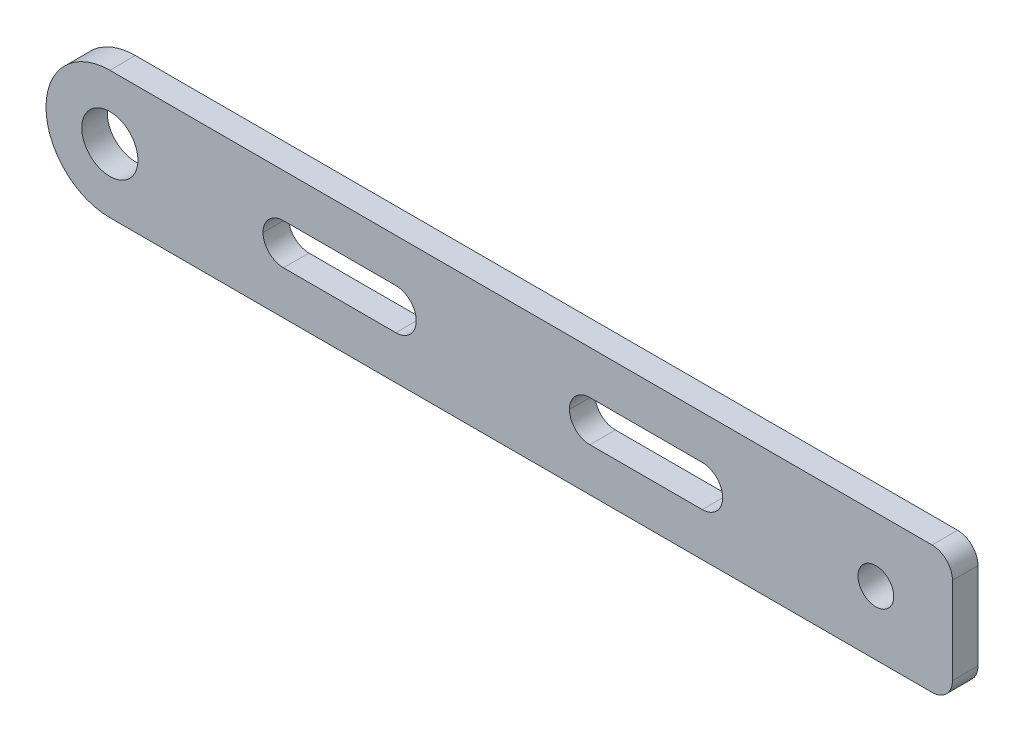
SolidWorks part; units mm, degrees
ref_plane "Front Plane" through (0, 0, 0) normal (0, 0, 1) x (1, 0, 0)
ref_plane "Top Plane" through (0, 0, 0) normal (0, 1, 0) x (1, 0, 0)
ref_plane "Right Plane" through (0, 0, 0) normal (1, 0, 0) x (0, 0, -1)
sketch "Sketch1" plane through (0, 0, 0) normal (0, 0, 1) x (1, 0, 0)
  line L1 (87.5, -12.5) -> (-77.5, -12.5)
  line L2 (87.5, -12.5) -> (87.5, 12.5)
  line L3 (87.5, 12.5) -> (-77.5, 12.5)
  line L5 (87.5, -12.5) -> (-87.5, 12.5) construction
  line L6 (87.5, 12.5) -> (-87.5, -12.5) construction
  circle A4 centre (-77.5, 0) radius 5.5
  circle A5 centre (72.5, 0) radius 3.5
  arc A13 (-77.5, 12.5) -> (-77.5, -12.5) centre (-77.5, 0) ccw
  point P0 (0, 0)
  dimension "D3" = 12.5
  dimension "D6" = 11
  dimension "D7" = 7
  dimension "D1" = 150
  dimension "D2" = 25
  dimension "D4" = 72.5
  dimension "D5" = 12.5
  dimension "D8" = 15
  dimension "D9" = 12.5
  dimension "D10" = 12.5
extrude "Boss-Extrude1" add sketch "Sketch1" along normal blind 5
sketch "Sketch2" plane through (0, 0, 0) normal (0, 0, -1) x (-1, 0, 0)
  line L0 (-87.5, -12.5) -> (-87.5, 12.5) construction
  line L1 (-42.5, 4) -> (-12.5, 4)
  line L2 (-42.5, 4) -> (-42.5, -4)
  line L3 (-42.5, -4) -> (-12.5, -4)
  line L4 (-12.5, 4) -> (-12.5, -4)
  line L5 (17.5, 4) -> (47.5, 4)
  line L6 (17.5, 4) -> (17.5, -4)
  line L7 (17.5, -4) -> (47.5, -4)
  line L8 (47.5, 4) -> (47.5, -4)
  line L10 (-87.5, 12.5) -> (77.5, 12.5) construction
  line L11 (77.5, -12.5) -> (-87.5, -12.5) construction
  dimension "D1" = 45
  dimension "D2" = 30
  dimension "D3" = 30
  dimension "D4" = 30
  dimension "D5" = 8.5
  dimension "D6" = 8.5
  dimension "D7" = 8.5
  dimension "D8" = 8.5
extrude "Cut-Extrude1" cut sketch "Sketch2" against normal blind 10
fillet "Fillet1" radius 4 10 edges at (12.5, -4, 2.5) (42.5, -4, 2.5) (42.5, 4, 2.5) (12.5, 4, 2.5) (-47.5, -4, 2.5) (-17.5, -4, 2.5) (-17.5, 4, 2.5) (-47.5, 4, 2.5) (87.5, 12.5, 2.5) (87.5, -12.5, 2.5)
